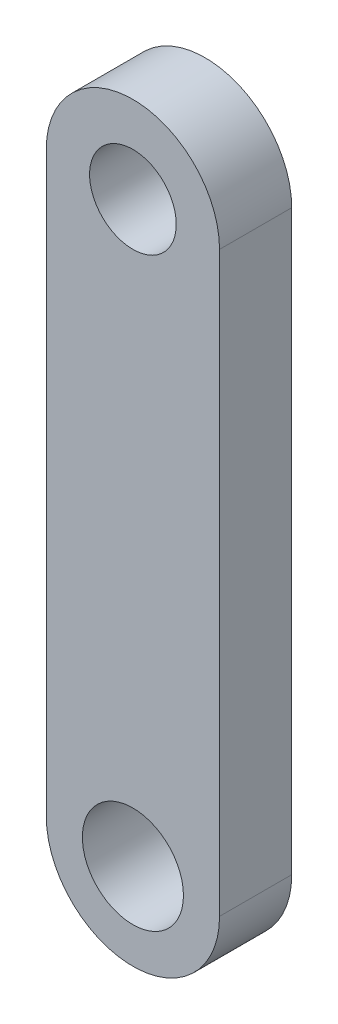
SolidWorks part; units mm, degrees
material "Stop 1060"
ref_plane "Płaszczyzna przednia" through (0, 0, 0) normal (0, 0, 1) x (1, 0, 0)
ref_plane "Płaszczyzna górna" through (0, 0, 0) normal (0, 1, 0) x (1, 0, 0)
ref_plane "Płaszczyzna prawa" through (0, 0, 0) normal (1, 0, 0) x (0, 0, -1)
sketch "Szkic1" plane through (0, 0, 0) normal (0, 0, 1) x (1, 0, 0)
  line L0 (0, 0) -> (0, -40)
  line L1 (-6, -40) -> (-6, 0)
  line L2 (6, -40) -> (6, 0)
  circle A0 centre (0, 0) radius 3
  arc A1 (6, 0) -> (-6, 0) centre (0, 0) ccw
  circle A2 centre (0, -40) radius 3.5
  arc A3 (-6, -40) -> (6, -40) centre (0, -40) ccw
  dimension "D1" = 6
  dimension "D2" = 12
  dimension "7" = 7
  dimension "D5" = 12
  dimension "D3" = 40
extrude "Dodanie-wyciągnięcie1" add sketch "Szkic1" along normal blind 5 contours L1 A3 L2 A1 A2 A0 region at (-5.4663, -20, 0)
